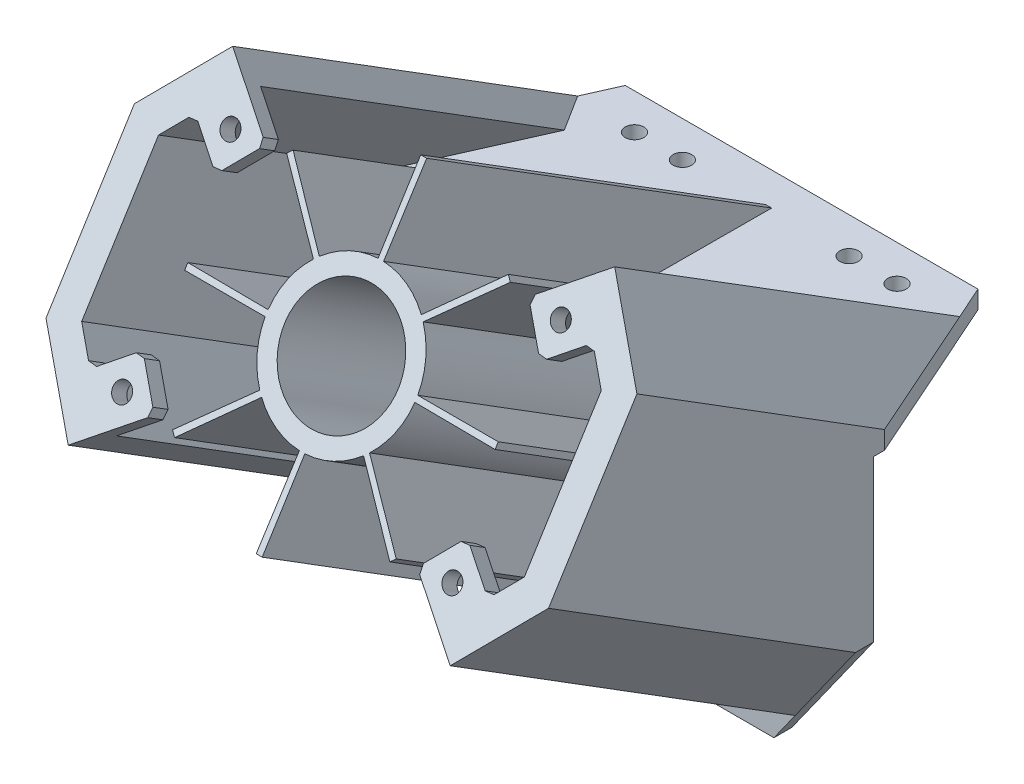
SolidWorks part; units mm, degrees
ref_plane "Front Plane" through (0, 0, 0) normal (0, 0, 1) x (1, 0, 0)
ref_plane "Top Plane" through (0, 0, 0) normal (0, 1, 0) x (1, 0, 0)
ref_plane "Right Plane" through (0, 0, 0) normal (1, 0, 0) x (0, 0, -1)
sketch "Sketch2" plane through (0, 0, 0) normal (0, 0, 1) x (1, 0, 0)
  line L0 (-110, 46) -> (-110, 49)
  line L2 (-110, 46) -> (-110, 0)
  line L3 (-110, 0) -> (-26, 0)
  line L4 (-136, 0) -> (0, 0)
  line L5 (0, 0) -> (0, 46)
  line L6 (0, 46) -> (-136, 46)
  line L7 (-136, 46) -> (-136, 0)
  line L8 (-136, 0) -> (0, 0)
  line L9 (0, 0) -> (0, 46)
  line L11 (-136, 46) -> (-136, 0)
  line L12 (-26, 46) -> (-26, 0)
  line L13 (-110, 49) -> (-26, 49)
  line L14 (-26, 49) -> (-26, 46)
  dimension "D2" = 5
  dimension "D3" = 5
  dimension "D4" = 3
  dimension "D1" = 0
extrude "Boss-Extrude1" add sketch "Sketch2" along normal blind 3 contours L13 L14 L12 L3 L2 L0
sketch "Sketch3" plane through (0, 0, 0) normal (0, 0, -1) x (-1, 0, 0)
  line L4 (0, 0) -> (136, 0)
  line L5 (0, 46) -> (0, 0)
  line L6 (136, 46) -> (0, 46)
  line L7 (136, 0) -> (136, 46)
  line L8 (0, 0) -> (136, 0)
  line L9 (0, 46) -> (0, 0)
  line L10 (136, 46) -> (0, 46)
  line L11 (136, 0) -> (136, 46)
  line M5 (110, 0) -> (110, 49)
  line M6 (110, 49) -> (26, 49)
  line M7 (26, 49) -> (26, 0)
  dimension "D1" = 0
extrude "Boss-Extrude2" add sketch "Sketch3" along normal blind 30 contours L10 M5 M6 M7 region at (-68, 47.5, 0)
sketch "Sketch4" plane through (-110, 0, 0) normal (-1, 0, 0) x (0, 0, 1)
  line L0 (3, 5) -> (-24.4943, 49)
  line L1 (3, 0) -> (3, 49) construction
  line L2 (3, 49) -> (-30, 49) construction
  dimension "D1" = 5
  dimension "D2" = 32
sketch "Sketch5" plane through (-26, 0, 0) normal (1, 0, 0) x (0, 0, -1)
  line L0 (-3, 5) -> (24.4943, 49) construction
  line L1 (-3, 5) -> (24.4943, 49)
ref_plane "Plane1" through (0, 2.7523, 4.4045) normal (0, 0.5299, 0.848) x (1, 0, 0)
sketch "Sketch6" plane through (0, 2.7523, 4.4045) normal (0, 0.5299, 0.848) x (1, 0, 0)
  line L0 (-110, 39.9646) -> (-110, -1.5898) construction
  line L1 (-110, -1.5898) -> (-26, -1.5898) construction
  line L2 (-26, -1.5898) -> (-26, 39.9646) construction
  line L3 (-26, 39.9646) -> (-26, 57.4519) construction
  line L4 (-26, 57.4519) -> (-110, 57.4519) construction
  line L5 (-110, 57.4519) -> (-110, 39.9646) construction
  line L6 (-110, 39.9646) -> (-110, -1.5898)
  line L7 (-110, -1.5898) -> (-26, -1.5898)
  line L8 (-26, -1.5898) -> (-26, 39.9646)
  line L9 (-26, 39.9646) -> (-26, 57.4519)
  line L10 (-26, 57.4519) -> (-110, 57.4519)
  line L11 (-110, 57.4519) -> (-110, 39.9646)
ref_point "Point1"
ref_point "Point2"
sketch "Sketch7" plane through (0, 2.7523, 4.4045) normal (0, 0.5299, 0.848) x (1, 0, 0)
  line L0 (-26, 2.6505) -> (-110, 2.6505)
  line L1 (-26, 54.5343) -> (-110, 54.5343)
  line L2 (-110, 42.5343) -> (-110, 14.6505)
  line L3 (-110, 42.5343) -> (-99.9308, 54.5343)
  line L4 (-110, 14.6505) -> (-99.9308, 2.6505)
  line L5 (-105, 40.7145) -> (-96.1006, 51.3204)
  line L6 (-110, 39.9646) -> (-110, -1.5898)
  line L7 (-110, -1.5898) -> (-26, -1.5898)
  line L8 (-26, -1.5898) -> (-26, 39.9646)
  line L9 (-26, 39.9646) -> (-26, 57.4519)
  line L10 (-26, 57.4519) -> (-110, 57.4519)
  line L11 (-110, 57.4519) -> (-110, 39.9646)
  line L12 (-105, 40.7145) -> (-105, 16.4703)
  line L13 (-110, -1.5898) -> (-26, -1.5898)
  line L14 (-26, -1.5898) -> (-26, 39.9646)
  line L15 (-26, 39.9646) -> (-26, 57.4519)
  line L16 (-26, 57.4519) -> (-110, 57.4519)
  line L17 (-105, 16.4703) -> (-96.1006, 5.8644)
  line L18 (-99.9308, 54.5343) -> (-96.1006, 51.3204)
  line L19 (-99.9308, 2.6505) -> (-96.1006, 5.8644)
  line L20 (-68, 54.5343) -> (-68, 2.6505) construction
  line L21 (-36.0692, 2.6505) -> (-39.8994, 5.8644)
  line L22 (-31, 16.4703) -> (-39.8994, 5.8644)
  line L23 (-26, 14.6505) -> (-36.0692, 2.6505)
  line L24 (-26, 42.5343) -> (-26, 14.6505)
  line L25 (-31, 40.7145) -> (-31, 16.4703)
  line L26 (-31, 40.7145) -> (-39.8994, 51.3204)
  line L27 (-36.0692, 54.5343) -> (-39.8994, 51.3204)
  line L28 (-26, 42.5343) -> (-36.0692, 54.5343)
  dimension "D1" = 0
  dimension "D2" = 12
  dimension "D3" = 12
  dimension "D4" = 40
  dimension "D5" = 5
extrude "Boss-Extrude3" add sketch "Sketch7" along normal blind 68 contours L4 L19 L17 L12 L5 L18 L3 L2 | L15 L28 L27 L26 L25 L22 L21 L23 L14 region at (-30.9667, 27, -10.7471) region at (-105.0333, 27, -10.7471)
sketch "Sketch8" plane through (0, 2.7523, 4.4045) normal (0, 0.5299, 0.848) x (1, 0, 0)
  line L0 (-110, -1.5898) -> (-26, -1.5898) construction
  line L1 (-26, -1.5898) -> (-26, 39.9646) construction
  line L2 (-26, 39.9646) -> (-26, 57.4519) construction
  line L3 (-26, 57.4519) -> (-110, 57.4519) construction
  line L4 (-68, 54.5343) -> (-68.5, 54.5343)
  line L6 (-110, -1.5898) -> (-26, -1.5898)
  line L7 (-26, -1.5898) -> (-26, 39.9646)
  line L8 (-39.8994, 5.8644) -> (-36.0692, 2.6505)
  line L9 (-31, 16.4703) -> (-39.8994, 5.8644)
  line L10 (-31, 40.7145) -> (-31, 16.4703)
  line L11 (-39.8994, 51.3204) -> (-31, 40.7145)
  line L12 (-36.0692, 54.5343) -> (-39.8994, 51.3204)
  line L13 (-26, 42.5343) -> (-36.0692, 54.5343)
  line L14 (-26, 14.6505) -> (-26, 42.5343)
  line L15 (-36.0692, 2.6505) -> (-26, 14.6505)
  line L16 (-39.8994, 5.8644) -> (-36.0692, 2.6505)
  line L17 (-31, 16.4703) -> (-39.8994, 5.8644)
  line L18 (-31, 40.7145) -> (-31, 16.4703)
  line L19 (-39.8994, 51.3204) -> (-31, 40.7145)
  line L20 (-36.0692, 54.5343) -> (-39.8994, 51.3204)
  line L21 (-26, 42.5343) -> (-36.0692, 54.5343)
  line L22 (-26, 14.6505) -> (-26, 42.5343)
  line L23 (-36.0692, 2.6505) -> (-26, 14.6505)
  line L24 (-105, 40.7145) -> (-96.1006, 51.3204)
  line L25 (-96.1006, 51.3204) -> (-99.9308, 54.5343)
  line L26 (-99.9308, 54.5343) -> (-110, 42.5343)
  line L27 (-110, 42.5343) -> (-110, 14.6505)
  line L28 (-110, 14.6505) -> (-99.9308, 2.6505)
  line L29 (-99.9308, 2.6505) -> (-96.1006, 5.8644)
  line L30 (-96.1006, 5.8644) -> (-105, 16.4703)
  line L31 (-105, 16.4703) -> (-105, 40.7145)
  line L32 (-105, 40.7145) -> (-96.1006, 51.3204)
  line L33 (-96.1006, 51.3204) -> (-99.9308, 54.5343)
  line L34 (-99.9308, 54.5343) -> (-110, 42.5343)
  line L35 (-110, 42.5343) -> (-110, 14.6505)
  line L36 (-110, 14.6505) -> (-99.9308, 2.6505)
  line L37 (-99.9308, 2.6505) -> (-96.1006, 5.8644)
  line L38 (-96.1006, 5.8644) -> (-105, 16.4703)
  line L39 (-105, 16.4703) -> (-105, 40.7145)
  line L40 (-26, 39.9646) -> (-26, 57.4519)
  line L41 (-26, 57.4519) -> (-110, 57.4519)
  line L42 (-110, 28.5924) -> (-26, 28.5924) construction
  line L44 (-99.9308, 54.5343) -> (-36.0692, 54.5343) construction
  line L45 (-68, 54.5343) -> (-67.5, 54.5343)
  line L46 (-68.5, 54.5343) -> (-68.5, 41.0824)
  line L48 (-67.5833, 41.0855) -> (-67.5, 54.5343)
  line L49 (-49.6563, 46.9361) -> (-49.3027, 46.5826)
  line L50 (-49.6563, 46.9361) -> (-50.0098, 47.2897)
  line L51 (-50.0098, 47.2897) -> (-59.5218, 37.7777)
  line L52 (-58.8714, 37.1317) -> (-49.3027, 46.5826)
  line L53 (-42.0581, 28.5924) -> (-42.0581, 28.0924)
  line L54 (-42.0581, 28.5924) -> (-42.0581, 29.0924)
  line L55 (-42.0581, 29.0924) -> (-55.51, 29.0924)
  line L56 (-55.5069, 28.1757) -> (-42.0581, 28.0924)
  line L57 (-49.6563, 10.2487) -> (-50.0098, 9.8951)
  line L58 (-49.6563, 10.2487) -> (-49.3027, 10.6022)
  line L59 (-49.3027, 10.6022) -> (-58.8147, 20.1142)
  line L60 (-59.4607, 19.4639) -> (-50.0098, 9.8951)
  line L61 (-68, 2.6505) -> (-68.5, 2.6505)
  line L62 (-68, 2.6505) -> (-67.5, 2.6505)
  line L63 (-67.5, 2.6505) -> (-67.5, 16.1024)
  line L64 (-68.4167, 16.0994) -> (-68.5, 2.6505)
  line L65 (-86.3437, 10.2487) -> (-86.6973, 10.6022)
  line L66 (-86.3437, 10.2487) -> (-85.9902, 9.8951)
  line L67 (-85.9902, 9.8951) -> (-76.4782, 19.4071)
  line L68 (-77.1286, 20.0531) -> (-86.6973, 10.6022)
  line L69 (-93.9419, 28.5924) -> (-93.9419, 29.0924)
  line L70 (-93.9419, 28.5924) -> (-93.9419, 28.0924)
  line L71 (-93.9419, 28.0924) -> (-80.49, 28.0924)
  line L72 (-80.4931, 29.0091) -> (-93.9419, 29.0924)
  line L73 (-86.3437, 46.9361) -> (-85.9902, 47.2897)
  line L74 (-86.3437, 46.9361) -> (-86.6973, 46.5826)
  line L75 (-86.6973, 46.5826) -> (-77.1853, 37.0706)
  line L76 (-76.5393, 37.721) -> (-85.9902, 47.2897)
  circle A0 centre (-68, 28.5924) radius 12.5
  circle A1 centre (-68, 28.5924) radius 9.5
  point P25 (-68, 28.5924)
  point P71 (-68, 28.5924)
  dimension "D3" = 25
  dimension "D4" = 3
  dimension "D5" = 0.5
  dimension "D6" = 0.5
  dimension "D7" = 8
  dimension "D1" = 0
  dimension "D2" = 0
extrude "Boss-Extrude4" add sketch "Sketch8" along normal blind 68 contours A0 A1 | A0 L52 L49 L50 L51 | A0 L48 L45 L4 L46 | A0 L76 L73 L74 L75 | A0 L72 L69 L70 L71 | A0 L68 L65 L66 L67 | A0 L64 L61 L62 L63 | A0 L60 L57 L58 L59 | A0 L56 L53 L54 L55 region at (-68.0205, 43.3817, -20.9835) region at (-68.0405, 37.3007, -17.1837) region at (-81.6737, 38.5713, -17.9777) region at (-54.3554, 38.5959, -17.9931) region at (-87.3169, 26.9826, -10.7362) region at (-48.6831, 27.0174, -10.758) region at (-81.6446, 15.4041, -3.5012) region at (-54.3263, 15.4287, -3.5166) region at (-67.9795, 10.6183, -0.5107)
sketch "Sketch9" plane through (-110, 0, 0) normal (-1, 0, 0) x (0, 0, 1)
  line L0 (0, 0) -> (0, 46)
  line L1 (0, 46) -> (-30, 46)
  line L2 (-30, 46) -> (-30, 0)
  line L3 (-30, 0) -> (0, 0)
extrude "Cut-Extrude3" cut sketch "Sketch9" against normal through all
sketch "Sketch11" plane through (0, 49, 0) normal (0, 1, 0) x (1, 0, 0)
  line L0 (-26, 1.8493) -> (-36.0692, 24.4943)
  line L1 (-36.0692, 24.4943) -> (-38.5174, 30)
  line L2 (-110, 30) -> (-26, 30) construction
  line L3 (-38.5174, 30) -> (-26, 30)
  line L4 (-26, 30) -> (-26, 1.8493)
  line L5 (-110, 1.8493) -> (-99.9308, 24.4943)
  line L6 (-99.9308, 24.4943) -> (-97.4826, 30)
  line L7 (-97.4826, 30) -> (-110, 30)
  line L8 (-110, 30) -> (-110, 1.8493)
extrude "Cut-Extrude4" cut sketch "Sketch11" against normal blind 68
sketch "Sketch12" plane through (0, 0, 3) normal (0, 0, 1) x (1, 0, 0)
  line L0 (-110, 19.1501) -> (-99.9308, 5)
  line L1 (-99.9308, 5) -> (-96.3728, 0)
  line L2 (-110, 0) -> (-26, 0) construction
  line L3 (-96.3728, 0) -> (-110, 0)
  line L4 (-110, 0) -> (-110, 19.1501)
  line L5 (-26, 19.1501) -> (-36.0692, 5)
  line L6 (-36.0692, 5) -> (-39.6272, 0)
  line L7 (-39.6272, 0) -> (-26, 0)
  line L8 (-26, 0) -> (-26, 19.1501)
extrude "Cut-Extrude5" cut sketch "Sketch12" against normal blind 68
sketch "Sketch13" plane through (-81.6645, 58.1122, -36.3125) normal (0.766, -0.5451, 0.3406) x (0.2775, -0.1975, -0.9402)
  line L0 (-75.7166, 11.3449) -> (-73.0106, 10.0496)
  line L1 (-75.7166, 11.3449) -> (-19.0207, -15.7942) construction
  line L2 (-73.0106, 10.0496) -> (-76.4647, 2.8337)
  line L3 (-76.4647, 2.8337) -> (-79.1707, 4.129)
  line L4 (-81.6944, -1.1432) -> (-75.7166, 11.3449) construction
  line L5 (-79.1707, 4.129) -> (-75.7166, 11.3449)
  dimension "D1" = 3
  dimension "D2" = 8
extrude "Boss-Extrude5" add sketch "Sketch13" along normal blind 8
chamfer "Chamfer1" distance 1 angle 45 3 edges at (-101.2429, 76.3169, 36.8516) (-95.1145, 71.956, 39.5766) (-89.9722, 77.1531, 36.3291)
sketch "Sketch14" plane through (-53.5065, -38.075, 23.7919) normal (0.766, 0.5451, -0.3406) x (-0.2775, -0.1975, -0.9402)
  line L0 (-37.4093, 91.3722) -> (-34.7034, 90.0769)
  line L1 (-37.4093, 91.3722) -> (22.1144, 62.8795) construction
  line L2 (-34.7034, 90.0769) -> (-31.2493, 97.2928)
  line L3 (-31.2493, 97.2928) -> (-33.9552, 98.5881)
  line L4 (-31.4316, 103.8602) -> (-37.4093, 91.3722) construction
  line L5 (-37.4093, 91.3722) -> (-33.9552, 98.5881)
  dimension "D1" = 3
  dimension "D2" = 8
extrude "Boss-Extrude6" add sketch "Sketch14" along normal blind 8
chamfer "Chamfer2" distance 1 angle 45 3 edges at (-89.9722, 47.3261, 54.9671) (-95.1145, 52.5233, 51.7195) (-101.2429, 48.1623, 54.4445)
sketch "Sketch15" plane through (1.8564, 1.321, -0.8255) normal (-0.766, -0.5451, 0.3406) x (0.2775, 0.1975, 0.9402)
  line L0 (37.9724, 90.1959) -> (35.2664, 88.9006)
  line L1 (37.9724, 90.1959) -> (-18.7235, 63.0568) construction
  line L2 (35.2664, 88.9006) -> (38.7205, 81.6847)
  line L3 (38.7205, 81.6847) -> (41.4265, 82.98)
  line L4 (43.9502, 77.7078) -> (37.9724, 90.1959) construction
  line L5 (41.4265, 82.98) -> (37.9724, 90.1959)
  dimension "D1" = 8
  dimension "D2" = 3
extrude "Boss-Extrude7" add sketch "Sketch15" along normal blind 8
chamfer "Chamfer3" distance 1 angle 45 3 edges at (-34.7571, 76.3169, 36.8516) (-40.8855, 71.956, 39.5766) (-46.0278, 77.1531, 36.3291)
sketch "Sketch16" plane through (-26.3016, 18.7161, -11.6951) normal (-0.766, 0.5451, -0.3406) x (-0.2775, 0.1975, 0.9402)
  line L0 (75.1535, 12.5212) -> (72.4476, 11.2259)
  line L1 (75.1535, 12.5212) -> (15.6298, -15.9715) construction
  line L2 (72.4476, 11.2259) -> (68.9935, 18.4418)
  line L3 (68.9935, 18.4418) -> (71.6994, 19.7371)
  line L4 (69.1758, 25.0092) -> (75.1535, 12.5212) construction
  line L5 (71.6994, 19.7371) -> (75.1535, 12.5212)
  dimension "D1" = 8
  dimension "D2" = 3
extrude "Boss-Extrude8" add sketch "Sketch16" along normal blind 8
chamfer "Chamfer4" distance 1 angle 45 3 edges at (-34.7571, 48.1623, 54.4445) (-46.0278, 47.3261, 54.9671) (-40.8855, 52.5233, 51.7195)
sketch "Sketch17" plane through (0, 38.7868, 62.0718) normal (0, 0.5299, 0.848) x (1, 0, 0)
  circle A0 centre (-95.6076, 45.6851) radius 1.55
  circle A1 centre (-95.6076, 11.4997) radius 1.55
  circle A2 centre (-40.3924, 45.6851) radius 1.55
  circle A3 centre (-40.3924, 11.4997) radius 1.55
  point P0 (-95.6076, 45.6851)
  point P1 (-95.6076, 11.4997)
  point P2 (-40.3924, 11.4997)
  point P3 (-40.3924, 45.6851)
  dimension "D1" = 3.1
  dimension "D2" = 3.1
  dimension "D3" = 3.1
  dimension "D4" = 3.1
extrude "Cut-Extrude6" cut sketch "Sketch17" against normal up to next
sketch "Sketch18" plane through (0, 49, 0) normal (0, 1, 0) x (1, 0, 0)
  line L0 (-97.4826, 30) -> (-38.5174, 30) construction
  line L1 (-68, 30) -> (-68, 26.0807) construction
  circle A0 centre (-89.9308, 24) radius 1.55
  circle A1 centre (-81.9308, 24) radius 1.55
  circle A2 centre (-54.0692, 24) radius 1.55
  circle A3 centre (-46.0692, 24) radius 1.55
  point P7 (-68, 30)
  dimension "D1" = 10
  dimension "D3" = 3.1
  dimension "D4" = 3.1
  dimension "D2" = 6
  dimension "D5" = 8
extrude "Cut-Extrude7" cut sketch "Sketch18" against normal up to next
sketch "Sketch19" plane through (0, 0, 3) normal (0, 0, 1) x (1, 0, 0)
  line L0 (-88.3808, 49) -> (-91.4808, 49) construction
  line L1 (-80.3808, 49) -> (-83.4808, 49) construction
  line L4 (-88.3808, 49) -> (-91.4808, 49)
  line L5 (-80.3808, 49) -> (-83.4808, 49)
  line L6 (-68, 0) -> (-68, 3.332) construction
  line L8 (-89.9308, 49) -> (-89.9308, 0) construction
  line L9 (-96.3728, 0) -> (-39.6272, 0) construction
  line L10 (-81.9308, 49) -> (-81.9308, 0) construction
  circle A0 centre (-89.9308, 8) radius 1.55
  circle A2 centre (-46.0692, 8) radius 1.55
  dimension "D1" = 8
extrude "Cut-Extrude8" cut sketch "Sketch19" against normal up to next contours A2 | A0
